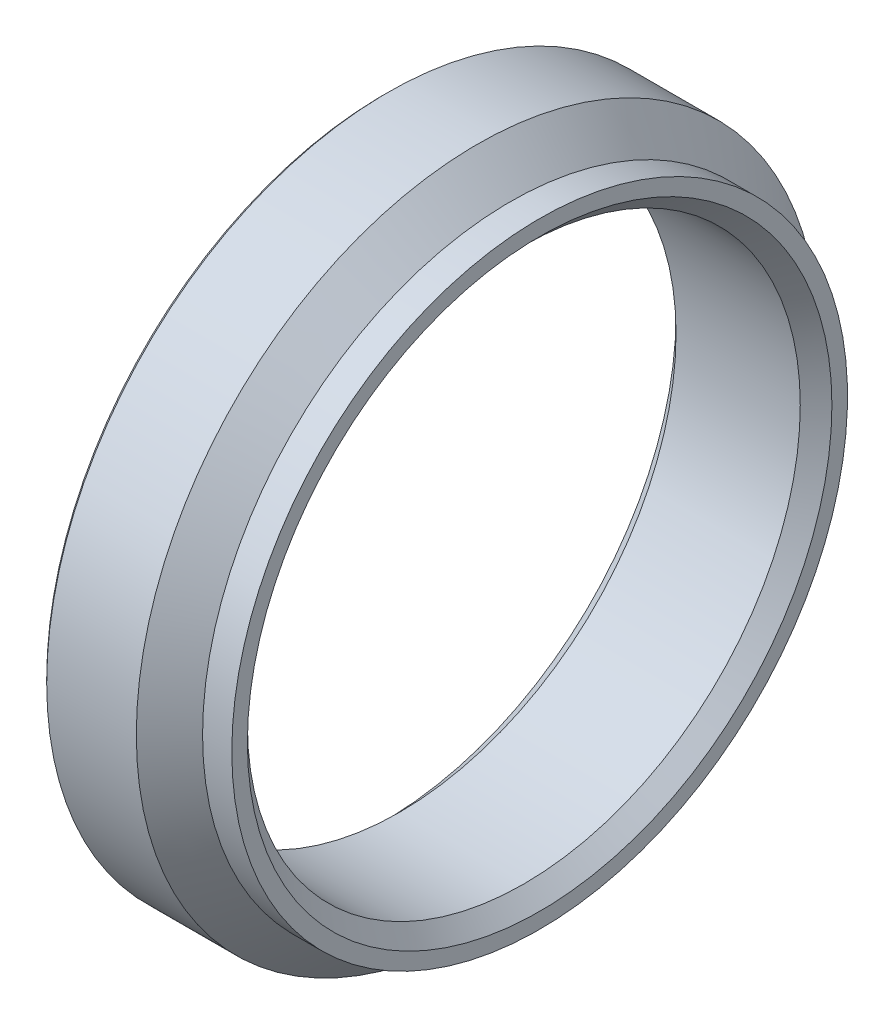
SolidWorks part; units mm, degrees
ref_plane "Front Plane" through (0, 0, 0) normal (0, 0, 1) x (1, 0, 0)
ref_plane "Top Plane" through (0, 0, 0) normal (0, 1, 0) x (1, 0, 0)
ref_plane "Right Plane" through (0, 0, 0) normal (1, 0, 0) x (0, 0, -1)
sketch "Sketch1" plane through (0, 0, 0) normal (0, 0, 1) x (1, 0, 0)
  line L0 (-8, 17.5) -> (-8, 15)
  line L1 (-8, 15) -> (-7.188, 14.188)
  line L2 (-7.188, 14.188) -> (-0.812, 14.188)
  line L3 (-0.812, 14.188) -> (0, 15)
  line L4 (0, 15) -> (0, 15.8)
  line L5 (0, 15.8) -> (-1.5, 15.8)
  line L6 (-1.5, 15.8) -> (-3.2, 17.5)
  line L7 (-3.2, 17.5) -> (-8, 17.5)
  line L8 (50, 0) -> (-50, 0) construction
revolve "Revolve1" add sketch "Sketch1" angle 360 about L8 reverse direction yes
cosmetic thread "Cosmetic Thread1"
sketch "Sketch2" plane through (0, 0, 0) normal (0, 0, 1) x (1, 0, 0)
  line L0 (-8, 17.3) -> (-7.8, 17.5)
  line L1 (-7.8, 17.5) -> (0, 17.5)
  line L2 (0, 17.5) -> (0, 20)
  line L3 (0, 20) -> (-8, 20)
  line L4 (-8, 20) -> (-8, 17.3)
  line L5 (50, 0) -> (-50, 0) construction
revolve "Cut-Revolve1" cut sketch "Sketch2" angle 360 about L5 reverse direction yes
ref_plane "ANBAU XY" through (0, 0, 0) normal (-1, 0, 0) x (0, 0, 1)
ref_plane "ANBAU XZ" through (0, 0, 0) normal (0, 1, 0) x (1, 0, 0)
ref_plane "ANBAU YZ" through (0, 0, 0) normal (0, 0, -1) x (-1, 0, 0)
ref_axis "ANBAU X" through (0, 0, 80.9) along (0, 0, -1)
ref_axis "ANBAU Y" through (0, 50, 0) along (0, -1, 0)
ref_axis "ANBAU Z" through (-80.9, 0, 0) along (1, 0, 0)
sketch3d "ANBAU"
  point P0 (0, 0, 0)
